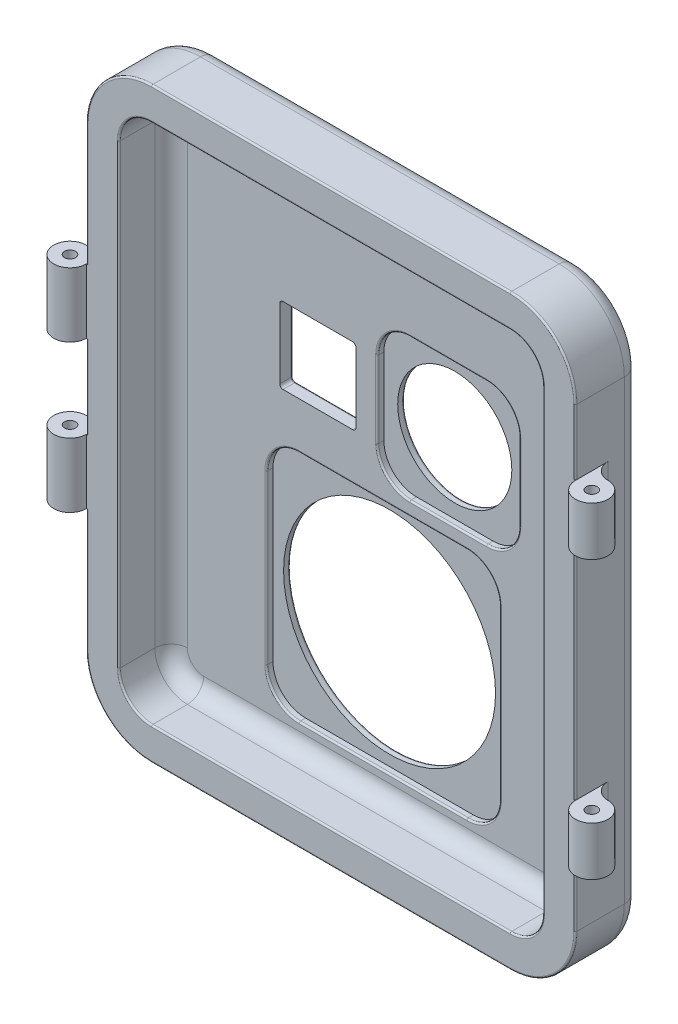
SolidWorks part; units mm, degrees
ref_plane "Front Plane" through (0, 0, 0) normal (0, 0, 1) x (1, 0, 0)
ref_plane "Top Plane" through (0, 0, 0) normal (0, 1, 0) x (1, 0, 0)
ref_plane "Right Plane" through (0, 0, 0) normal (1, 0, 0) x (0, 0, -1)
sketch "Sketch1" plane through (0, 0, 0) normal (0, 0, 1) x (1, 0, 0)
  line L3 (55, -90) -> (-55, -90)
  line L4 (75, -70) -> (75, 70)
  line L5 (55, 90) -> (-55, 90)
  line L6 (-75, -70) -> (-75, 70)
  line L7 (75, -90) -> (-75, 90) construction
  line L8 (75, 90) -> (-75, -90) construction
  arc A2 (-55, -90) -> (-75, -70) centre (-55, -70) cw
  arc A3 (55, -90) -> (75, -70) centre (55, -70) ccw
  arc A4 (75, 70) -> (55, 90) centre (55, 70) ccw
  arc A5 (-55, 90) -> (-75, 70) centre (-55, 70) ccw
  point P0 (0, 0)
  dimension "D3" = 20
  dimension "D1" = 180
  dimension "D2" = 150
extrude "Boss-Extrude1" add sketch "Sketch1" along normal blind 20
shell "Shell1" thickness 10 removed face at (0, 0, 20)
sketch "Sketch8" plane through (0, 0, 4) normal (0, 0, 1) x (1, 0, 0)
  line L0 (75.1597, 25) -> (-92.0515, 25) construction
  dimension "D1" = 25
sketch "Sketch2" plane through (0, 0, 20) normal (0, 0, 1) x (1, 0, 0)
  line L10 (-72, 70) -> (-72, -70)
  line L11 (-55, -87) -> (55, -87)
  line L12 (72, -70) -> (72, 70)
  line L13 (55, 87) -> (-55, 87)
  line L14 (-70, 70) -> (-70, -70)
  line L15 (-55, -85) -> (55, -85)
  line L16 (70, -70) -> (70, 70)
  line L17 (55, 85) -> (-55, 85)
  line L18 (-70, 70) -> (-70, -70) construction
  line L19 (-55, -85) -> (55, -85) construction
  line L20 (70, -70) -> (70, 70) construction
  line L21 (55, 85) -> (-55, 85) construction
  line L22 (-68, 70) -> (-68, -70)
  line L23 (-55, -83) -> (55, -83)
  line L24 (68, -70) -> (68, 70)
  line L25 (55, 83) -> (-55, 83)
  arc A8 (-72, -70) -> (-55, -87) centre (-55, -70) ccw
  arc A9 (55, -87) -> (72, -70) centre (55, -70) ccw
  arc A10 (72, 70) -> (55, 87) centre (55, 70) ccw
  arc A11 (-55, 87) -> (-72, 70) centre (-55, 70) ccw
  arc A12 (-55, 85) -> (-70, 70) centre (-55, 70) ccw
  arc A13 (-70, -70) -> (-55, -85) centre (-55, -70) ccw
  arc A14 (55, -85) -> (70, -70) centre (55, -70) ccw
  arc A15 (70, 70) -> (55, 85) centre (55, 70) ccw
  arc A16 (-55, 85) -> (-70, 70) centre (-55, 70) ccw construction
  arc A17 (-70, -70) -> (-55, -85) centre (-55, -70) ccw construction
  arc A18 (55, -85) -> (70, -70) centre (55, -70) ccw construction
  arc A19 (70, 70) -> (55, 85) centre (55, 70) ccw construction
  arc A20 (-68, -70) -> (-55, -83) centre (-55, -70) ccw
  arc A21 (55, -83) -> (68, -70) centre (55, -70) ccw
  arc A22 (68, 70) -> (55, 83) centre (55, 70) ccw
  arc A23 (-55, 83) -> (-68, 70) centre (-55, 70) ccw
  dimension "D1" = 5
  dimension "D2" = 2
  dimension "D3" = 2
extrude "Cut-Extrude1" [suppressed] cut sketch "Sketch2" against normal blind 3
sketch "Sketch3" plane through (0, 0, 0) normal (0, 0, 1) x (1, 0, 0)
  line L0 (-55, -80) -> (55, -80) construction
  circle A0 centre (0, -36.75) radius 32.5
  dimension "D2" = 65
  dimension "D1" = 43.25
extrude "Cut-Extrude5" cut sketch "Sketch3" along normal through all
sketch "Sketch4" plane through (0, 0, 0) normal (0, 0, 1) x (1, 0, 0)
  line L0 (75.1597, 25) -> (-92.0515, 25) construction
  line L1 (-30.675, 13.325) -> (-9.325, 13.325)
  line L2 (-31.675, 14.325) -> (-31.675, 35.675)
  line L3 (-30.675, 36.675) -> (-9.325, 36.675)
  line L4 (-8.325, 14.325) -> (-8.325, 35.675)
  line L5 (-31.675, 13.325) -> (-8.325, 36.675) construction
  line L6 (-31.675, 36.675) -> (-8.325, 13.325) construction
  arc A0 (-8.325, 14.325) -> (-9.325, 13.325) centre (-9.325, 14.325) cw
  arc A1 (-31.675, 35.675) -> (-30.675, 36.675) centre (-30.675, 35.675) cw
  arc A2 (-30.675, 13.325) -> (-31.675, 14.325) centre (-30.675, 14.325) cw
  arc A3 (-9.325, 36.675) -> (-8.325, 35.675) centre (-9.325, 35.675) cw
  point P0 (-20, 25)
  dimension "D3" = 1
  dimension "D1" = 23.35
  dimension "D2" = 20
extrude "Cut-Extrude6" cut sketch "Sketch4" along normal through all
sketch "Sketch5" plane through (0, 0, 0) normal (0, 0, 1) x (1, 0, 0)
  line L0 (75.1597, 25) -> (-92.0515, 25) construction
  circle A0 centre (20, 25) radius 17.5
  dimension "D1" = 35
  dimension "D2" = 20
extrude "Cut-Extrude7" cut sketch "Sketch5" along normal through all
sketch "Sketch6" plane through (0, 0, 0) normal (0, 1, 0) x (1, 0, 0)
  line L0 (75, -20) -> (75, 0) construction
  line L1 (75, -20) -> (75, -10)
  line L2 (55, -20) -> (-55, -20) construction
  arc A0 (75, -20) -> (80, -15) centre (80, -20) ccw
  circle A1 centre (80, -20) radius 1.7
  arc A2 (80, -15) -> (75, -10) centre (80, -10) cw
  dimension "D1" = 3.4
  dimension "D2" = 10
extrude "Boss-Extrude2" add sketch "Sketch6" along normal mid plane 100
extrude "Cut-Extrude8" cut sketch "Sketch6<2>" against normal mid plane 70
sketch "Sketch6<2>" plane through (0, 0, 0) normal (0, 1, 0) x (1, 0, 0) same geometry as "Sketch6"
sketch "Sketch9" plane through (0, 0, 0) normal (0, 1, 0) x (1, 0, 0)
  line L0 (55, -20) -> (-55, -20) construction
  line L1 (-75, -20) -> (-75, 0) construction
  line L2 (-75, -10) -> (-75, -20)
  circle A0 centre (-80, -20) radius 1.7
  arc A1 (-80, -15) -> (-75, -20) centre (-80, -20) ccw
  arc A2 (-80, -15) -> (-75, -10) centre (-80, -10) ccw
  dimension "D1" = 10
  dimension "D2" = 3.4
extrude "Boss-Extrude3" add sketch "Sketch9" along normal mid plane 65
extrude "Cut-Extrude10" cut sketch "Sketch9<2>" against normal mid plane 25.5
sketch "Sketch9<2>" plane through (0, 0, 0) normal (0, 1, 0) x (1, 0, 0) same geometry as "Sketch9"
sketch "Sketch7" plane through (0, 0, 4) normal (0, 0, 1) x (1, 0, 0)
  line L1 (-25.75, -1) -> (25.75, -1)
  line L2 (-35.75, -11) -> (-35.75, -62.5)
  line L3 (-25.75, -72.5) -> (25.75, -72.5)
  line L4 (35.75, -11) -> (35.75, -62.5)
  line L5 (-35.75, -1) -> (35.75, -72.5) construction
  line L6 (-35.75, -72.5) -> (35.75, -1) construction
  line L7 (8.25, 46.75) -> (31.75, 46.75)
  line L8 (-1.75, 36.75) -> (-1.75, 13.25)
  line L9 (8.25, 3.25) -> (31.75, 3.25)
  line L10 (41.75, 36.75) -> (41.75, 13.25)
  line L11 (-1.75, 46.75) -> (41.75, 3.25) construction
  line L12 (-1.75, 3.25) -> (41.75, 46.75) construction
  arc A1 (-35.75, -62.5) -> (-25.75, -72.5) centre (-25.75, -62.5) ccw
  arc A2 (25.75, -72.5) -> (35.75, -62.5) centre (25.75, -62.5) ccw
  arc A3 (25.75, -1) -> (35.75, -11) centre (25.75, -11) cw
  arc A4 (-25.75, -1) -> (-35.75, -11) centre (-25.75, -11) ccw
  arc A5 (-1.75, 13.25) -> (8.25, 3.25) centre (8.25, 13.25) ccw
  arc A6 (31.75, 3.25) -> (41.75, 13.25) centre (31.75, 13.25) ccw
  arc A7 (31.75, 46.75) -> (41.75, 36.75) centre (31.75, 36.75) cw
  arc A8 (8.25, 46.75) -> (-1.75, 36.75) centre (8.25, 36.75) ccw
  point P0 (0, -36.75)
  point P5 (20, 25)
  dimension "D1" = 43.5
  dimension "D5" = 10
  dimension "D2" = 43.5
  dimension "D3" = 71.5
  dimension "D4" = 71.5
extrude "Cut-Extrude9" cut sketch "Sketch7" against normal blind 2
fillet "Fillet1" radius 5 16 edges at (75, 0, 0) (69.1421, -84.1421, 0) (0, -90, 0) (-69.1421, -84.1421, 0) (-75, 0, 0) (-69.1421, 84.1421, 0) (0, 90, 0) (69.1421, 84.1421, 0) (0, 80, 4) (62.0711, 77.0711, 4) (65, 0, 4) (62.0711, -77.0711, 4) (0, -80, 4) (-62.0711, -77.0711, 4) (-65, 0, 4) (-62.0711, 77.0711, 4)
fillet "Fillet2" radius 0.5 46 edges at (-8.6179, 13.6179, 0) (-20, 13.325, 0) (-31.3821, 13.6179, 0) (-31.675, 25, 0) (-31.3821, 36.3821, 0) (-20, 36.675, 0) (-8.6179, 36.3821, 0) (75, 60, 20) (69.1421, 84.1421, 20) (0, 90, 20) (-69.1421, 84.1421, 20) (75, -60, 20) (69.1421, -84.1421, 20) (0, -90, 20) (-69.1421, -84.1421, 20) (-62.0711, 77.0711, 20) (0, 80, 20) (62.0711, 77.0711, 20) (65, 0, 20) (62.0711, -77.0711, 20) (0, -80, 20) (-62.0711, -77.0711, 20) (-8.325, 25, 0) (37.5, 25, 0) (75, 0, 20) (-75, 51.25, 20) (-75, -51.25, 20) (-75, 0, 20) (-65, 0, 20) (32.5, -36.75, 0) (1.1789, 43.8211, 4) (20, 46.75, 4) (38.8211, 43.8211, 4) (41.75, 25, 4) (38.8211, 6.1789, 4) (20, 3.25, 4) (1.1789, 6.1789, 4) (32.8211, -3.9289, 4) (35.75, -36.75, 4) (32.8211, -69.5711, 4) (0, -72.5, 4) (-32.8211, -69.5711, 4) (-35.75, -36.75, 4) (-32.8211, -3.9289, 4) (-1.75, 25, 4) (0, -1, 4)
